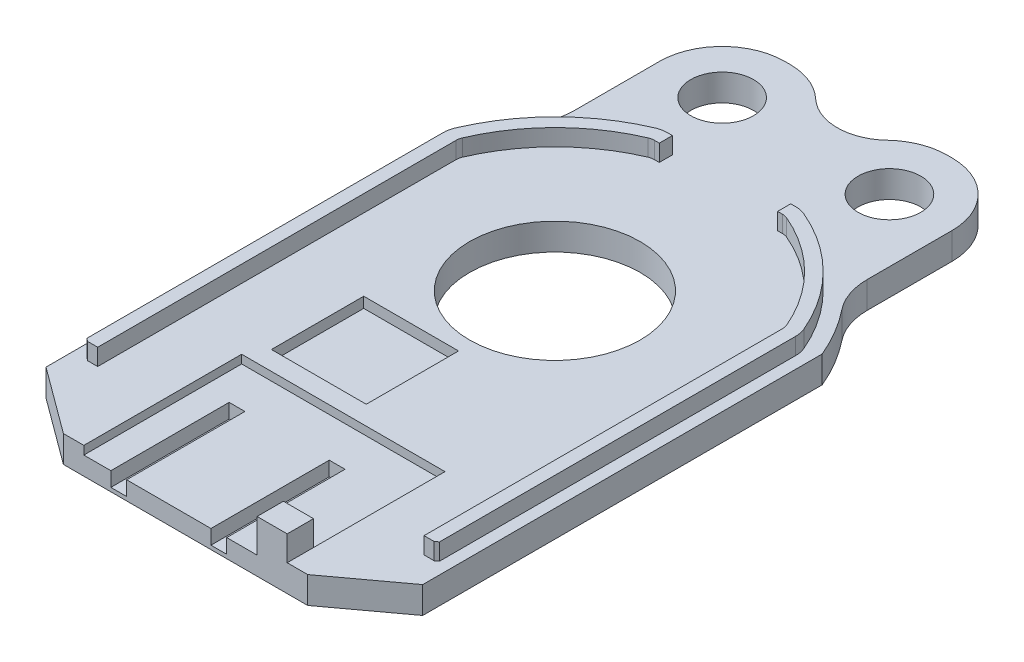
SolidWorks part; units mm, degrees
ref_plane "Front Plane" through (0, 0, 0) normal (0, 0, 1) x (1, 0, 0)
ref_plane "Top Plane" through (0, 0, 0) normal (0, 1, 0) x (1, 0, 0)
ref_plane "Right Plane" through (0, 0, 0) normal (1, 0, 0) x (0, 0, -1)
sketch "Sketch1" plane through (0, 0, 0) normal (0, 1, 0) x (1, 0, 0)
  line L0 (-14.3002, 5.9944) -> (-14.3002, -24.3332)
  line L1 (-14.3002, -24.3332) -> (-9.271, -28.0416)
  line L2 (-9.271, -28.0416) -> (9.271, -28.0416)
  line L3 (9.271, -28.0416) -> (14.3002, -24.3332)
  line L4 (14.3002, -24.3332) -> (14.3002, 5.9944)
  circle A0 centre (0, 0) radius 6.477
  arc A1 (-14.3002, 5.9944) -> (14.3002, 5.9944) centre (0, 0) cw
  dimension "D1" = 12.954
  dimension "D2" = 14.3002
  dimension "D3" = 14.3002
  dimension "D4" = 28.0416
  dimension "D5" = 5.0292
  dimension "D6" = 3.7084
  dimension "D7" = 3.7084
  dimension "D8" = 5.0292
  dimension "D9" = 34.036
extrude "Boss-Extrude1" add sketch "Sketch1" along normal blind 2.032
sketch "Sketch2" plane through (0, 2.032, 0) normal (0, 1, 0) x (1, 0, 0)
  line L0 (0, -28.0416) -> (-7.7191, -28.0416)
  line L1 (-9.271, -28.0416) -> (9.271, -28.0416) construction
  line L2 (0, -28.0416) -> (7.7191, -28.0416)
  line L3 (-7.7191, -28.0416) -> (-7.7191, -16.0604)
  line L4 (-7.7191, -16.0604) -> (7.7191, -16.0604)
  line L5 (7.7191, -16.0604) -> (7.7191, -28.0416)
  dimension "D1" = 7.7191
  dimension "D2" = 7.7191
  dimension "D3" = 11.9812
extrude "Cut-Extrude1" cut sketch "Sketch2" against normal blind 0.6401
sketch "Sketch3" plane through (0, 1.3919, 0) normal (0, 1, 0) x (1, 0, 0)
  line L0 (-7.7191, -28.0416) -> (7.7191, -28.0416) construction
  line L1 (-5.6693, -28.0416) -> (-4.4704, -28.0416)
  line L2 (-5.6693, -28.0416) -> (-5.6693, -19.0602)
  line L3 (-5.6693, -19.0602) -> (-4.4704, -19.0602)
  line L4 (-4.4704, -28.0416) -> (-4.4704, -19.0602)
  line L5 (-7.7191, -16.0604) -> (-7.7191, -28.0416) construction
  line L6 (1.9304, -28.0416) -> (3.1293, -28.0416)
  line L7 (1.9304, -28.0416) -> (1.9304, -19.0602)
  line L8 (1.9304, -19.0602) -> (3.1293, -19.0602)
  line L9 (3.1293, -28.0416) -> (3.1293, -19.0602)
  dimension "D1" = 2.0498
  dimension "D2" = 1.1989
  dimension "D3" = 6.4008
  dimension "D4" = 1.1989
  dimension "D5" = 8.9814
  dimension "D6" = 8.9814
extrude "Cut-Extrude2" cut sketch "Sketch3" against normal blind 1.0998
sketch "Sketch4" plane through (0, 2.032, 0) normal (0, 1, 0) x (1, 0, 0)
  line L0 (-7.7191, -16.0604) -> (-7.7191, -28.0416) construction
  line L1 (-6.8991, -14.6205) -> (0.2992, -14.6205)
  line L2 (-6.8991, -14.6205) -> (-6.8991, -7.6126)
  line L3 (-6.8991, -7.6126) -> (0.2992, -7.6126)
  line L4 (0.2992, -14.6205) -> (0.2992, -7.6126)
  line L5 (7.7191, -16.0604) -> (-7.7191, -16.0604) construction
  dimension "D1" = 0.8199
  dimension "D2" = 1.4399
  dimension "D3" = 7.0079
  dimension "D4" = 7.1984
extrude "Cut-Extrude3" cut sketch "Sketch4" against normal blind 0.8001
sketch "Sketch5" plane through (0, 2.032, 0) normal (0, 1, 0) x (1, 0, 0)
  line L0 (12.4028, -22.3342) -> (13.1717, -22.3342)
  line L1 (13.1717, -22.3342) -> (13.401, -22.1529)
  line L2 (13.401, -22.1529) -> (13.401, 4.8829)
  line L3 (12.4028, -22.3342) -> (12.4028, 4.8819)
  line L4 (7.7191, -28.0416) -> (9.271, -28.0416) construction
  line L5 (14.3002, -24.3332) -> (14.3002, 5.9944) construction
  line L6 (4.8793, 13.401) -> (4.5034, 13.401)
  line L7 (4.5034, 13.401) -> (4.5034, 12.4028)
  line L8 (4.5034, 12.4028) -> (4.8793, 12.4028)
  line L9 (0.0143, 14.8202) -> (0.0143, -25.5245) construction
  line L10 (-4.8508, 13.401) -> (-4.4748, 13.401)
  line L11 (-4.4748, 13.401) -> (-4.4748, 12.4028)
  line L12 (-4.4748, 12.4028) -> (-4.8508, 12.4028)
  line L13 (-12.3742, -22.3342) -> (-12.3742, 4.8819)
  line L14 (-12.3742, -22.3342) -> (-13.1431, -22.3342)
  line L15 (-13.1431, -22.3342) -> (-13.3725, -22.1529)
  line L16 (-13.3725, -22.1529) -> (-13.3725, 4.8829)
  arc A0 (5.2725, 12.3222) -> (12.3222, 5.2751) centre (0.0143, 0.0124) cw
  arc A1 (4.8793, 12.4028) -> (5.2725, 12.3222) centre (4.8793, 11.404) cw
  arc A2 (12.4028, 4.8819) -> (12.3222, 5.2751) centre (11.404, 4.8819) ccw
  arc A3 (5.6081, 13.2644) -> (13.2397, 5.6678) centre (0.0024, 0.0011) cw
  arc A4 (4.8793, 13.401) -> (5.6081, 13.2644) centre (4.8793, 11.3897) cw
  arc A5 (13.2397, 5.6678) -> (13.401, 4.8829) centre (11.4022, 4.8811) cw
  arc A6 (-5.5795, 13.2644) -> (-13.2112, 5.6678) centre (0.0262, 0.0011) ccw
  arc A7 (-4.8508, 13.401) -> (-5.5795, 13.2644) centre (-4.8508, 11.3897) ccw
  arc A8 (-4.8508, 12.4028) -> (-5.2439, 12.3222) centre (-4.8508, 11.404) ccw
  arc A9 (-5.2439, 12.3222) -> (-12.2936, 5.2751) centre (0.0143, 0.0124) ccw
  arc A10 (-12.3742, 4.8819) -> (-12.2936, 5.2751) centre (-11.3754, 4.8819) cw
  arc A11 (-13.2112, 5.6678) -> (-13.3725, 4.8829) centre (-11.3736, 4.8811) ccw
  dimension "D17" = 13.3858
  dimension "D22" = 14.3993
  dimension "D1" = 5.7074
  dimension "D2" = 0.2294
  dimension "D3" = 0.1814
  dimension "D4" = 0.8992
  dimension "D5" = 0.9982
  dimension "D6" = 27.2161
  dimension "D7" = 27.0358
  dimension "D8" = 7.8994
  dimension "D9" = 7.5209
  dimension "D10" = 0.9982
  dimension "D11" = 0.3759
  dimension "D12" = 0.3759
  dimension "D13" = 0.3932
  dimension "D14" = 0.0806
  dimension "D15" = 0.3932
  dimension "D16" = 0.0806
  dimension "D18" = 0.7287
  dimension "D19" = 0.1367
  dimension "D20" = 0.1613
  dimension "D21" = 0.7849
extrude "Boss-Extrude2" add sketch "Sketch5" along normal blind 1.27
sketch "Sketch6" plane through (0, 1.3919, 0) normal (0, 1, 0) x (1, 0, 0)
  line L1 (7.7191, -28.0416) -> (5.4331, -28.0416)
  line L2 (7.7191, -28.0416) -> (7.7191, -26.0426)
  line L3 (7.7191, -26.0426) -> (5.4331, -26.0426)
  line L4 (5.4331, -28.0416) -> (5.4331, -26.0426)
  dimension "D1" = 2.286
  dimension "D2" = 1.999
extrude "Boss-Extrude3" add sketch "Sketch6" along normal blind 2.54
sketch "Sketch7" plane through (0, 0, 0) normal (0, -1, 0) x (1, 0, 0)
  line L0 (-11.1125, -12.6011) -> (-11.1125, -19.05)
  line L1 (-6.35, -23.8125) -> (-5.9834, -23.8125)
  line L2 (11.1125, -19.05) -> (11.1125, -12.6011)
  line L3 (6.35, -23.8125) -> (5.9834, -23.8125)
  circle A0 centre (6.35, -19.05) radius 2.3813
  circle A1 centre (-6.35, -19.05) radius 2.3813
  arc A2 (-14.3002, -5.9944) -> (14.3002, -5.9944) centre (0, 0) ccw construction
  arc A3 (11.1125, -19.05) -> (6.35, -23.8125) centre (6.35, -19.05) cw
  arc A4 (-11.1125, -19.05) -> (-6.35, -23.8125) centre (-6.35, -19.05) ccw
  arc A6 (-2.7174, -22.5162) -> (-5.9834, -23.8125) centre (-5.9834, -19.05) cw
  arc A7 (-2.7174, -22.5162) -> (2.7174, -22.5162) centre (0, -25.4) cw
  arc A8 (2.7174, -22.5162) -> (5.9834, -23.8125) centre (5.9834, -19.05) ccw
  arc A9 (-12.1448, -9.6401) -> (-14.3002, -5.9944) centre (0, 0) cw
  arc A10 (-12.1448, -9.6401) -> (-11.1125, -12.6011) centre (-15.875, -12.6011) cw
  arc A11 (12.1448, -9.6401) -> (14.3002, -5.9944) centre (0, 0) ccw
  arc A12 (11.1125, -12.6011) -> (12.1448, -9.6401) centre (15.875, -12.6011) cw
  point P23 (3.6305, -23.8125)
  point P29 (-11.1125, -10.8139)
  point P35 (11.1125, -10.8139)
  arc M5 (-14.3002, -5.9944) -> (14.3002, -5.9944) centre (0, 0) ccw
  dimension "D5" = 4.7625
  dimension "D6" = 4.7625
  dimension "D10" = 4.7625
  dimension "D12" = 4.7625
  dimension "D13" = 4.7625
  dimension "D14" = 4.7625
  dimension "D15" = 4.7625
  dimension "D1" = 19.05
  dimension "D2" = 19.05
  dimension "D3" = 6.35
  dimension "D4" = 6.35
  dimension "D7" = 4.7625
  dimension "D8" = 4.7625
  dimension "D9" = 4.7625
  dimension "D11" = 25.4
extrude "Boss-Extrude4" add sketch "Sketch7" against normal blind 2.032 contours L0 A4 L1 A3 L2 A0 A1 M5 region at (0, 0, -18.1634)
